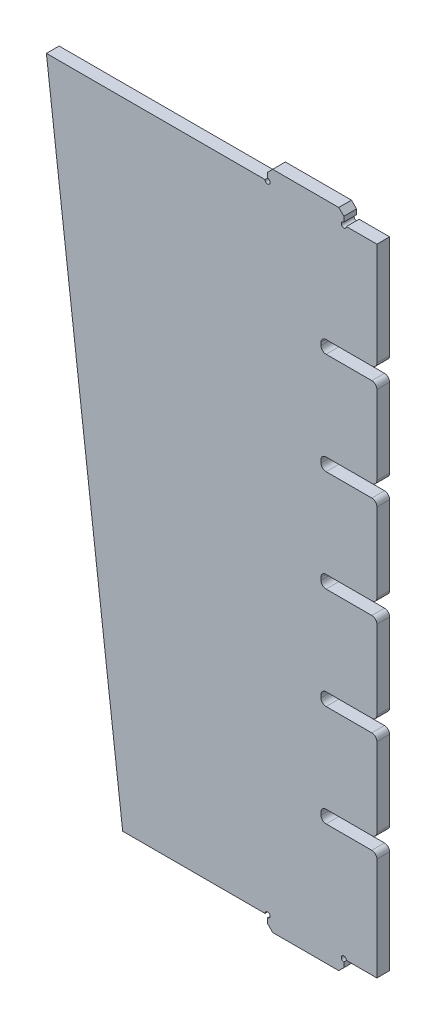
SolidWorks part; units mm, degrees
ref_plane "前基準面" through (0, 0, 0) normal (0, 0, 1) x (1, 0, 0)
ref_plane "上基準面" through (0, 0, 0) normal (0, 1, 0) x (1, 0, 0)
ref_plane "右基準面" through (0, 0, 0) normal (1, 0, 0) x (0, 0, -1)
sketch "草圖1" plane through (0, 0, 0) normal (0, 0, 1) x (1, 0, 0)
  line L0 (-15, 2) -> (-13, 0)
  line L3 (-13, 0) -> (13, 0)
  line L5 (13, 0) -> (15, 2)
  line L6 (-15, 2) -> (-15, 4)
  line L14 (28, 5) -> (28, 47.5)
  line L15 (-16, 5) -> (-72, 5)
  line L16 (15, 2) -> (15, 4)
  line L17 (16, 5) -> (28, 5)
  line L18 (-65, 130) -> (34.3333, 130) construction
  line L19 (16, 255) -> (28, 255)
  line L20 (15, 258) -> (15, 256)
  line L22 (-15, 258) -> (-15, 256)
  line L23 (13, 260) -> (15, 258)
  line L24 (-13, 260) -> (13, 260)
  line L25 (-15, 258) -> (-13, 260)
  line L26 (6, 172.5) -> (28, 172.5)
  line L27 (6, 212.5) -> (28, 212.5)
  line L28 (6, 212.5) -> (6, 207.5)
  line L29 (6, 207.5) -> (28, 207.5)
  line L31 (6, 172.5) -> (6, 167.5)
  line L32 (6, 167.5) -> (28, 167.5)
  line L34 (6, 132.5) -> (28, 132.5)
  line L35 (6, 132.5) -> (6, 127.5)
  line L36 (6, 127.5) -> (28, 127.5)
  line L38 (6, 92.5) -> (28, 92.5)
  line L39 (6, 92.5) -> (6, 87.5)
  line L40 (6, 87.5) -> (28, 87.5)
  line L42 (6, 52.5) -> (28, 52.5)
  line L43 (6, 52.5) -> (6, 47.5)
  line L44 (6, 47.5) -> (28, 47.5)
  line L46 (28, 212.5) -> (28, 255)
  line L47 (28, 172.5) -> (28, 207.5)
  line L48 (28, 132.5) -> (28, 167.5)
  line L49 (28, 92.5) -> (28, 127.5)
  line L50 (28, 52.5) -> (28, 87.5)
  line L51 (-16, 255) -> (-102, 255)
  line L52 (-102, 255) -> (-72, 5)
  arc A0 (-15, 4) -> (-16, 5) centre (-15, 5) ccw
  arc A1 (16, 5) -> (15, 4) centre (15, 5) ccw
  arc A2 (16, 255) -> (15, 256) centre (15, 255) cw
  arc A3 (-15, 256) -> (-16, 255) centre (-15, 255) cw
  point P1 (15, 0)
  point P2 (-15, 0)
  point P8 (0, 0)
  point P30 (-15, 260)
  point P31 (15, 260)
  point P49 (6, 130)
  dimension "D8" = 1
  dimension "D6" = 22
  dimension "D1" = 30
  dimension "D2" = 250
  dimension "D3" = 130
  dimension "D7" = 3
  dimension "D9" = 5
  dimension "D10" = 40
  dimension "D11" = 5
  dimension "D12" = 43
  dimension "D13" = 100
extrude "填料-伸長1" add sketch "草圖1" along normal mid plane 5 contours L52 L15 A0 L6 L0 L3 L5 L16 A1 L17 L14 L44 L43 L42 L50 L40 L39 L38 L49 L36 L35 L34 L48 L32 L31 L26 L47 L29 L28 L27 L46 L19 A2 L20 L23 L24 L25 L22 A3 L51
fillet "圓角1" radius 2 20 edges at (6, 52.5, 0) (6, 47.5, 0) (28, 47.5, 0) (28, 52.5, 0) (6, 92.5, 0) (6, 87.5, 0) (28, 87.5, 0) (28, 92.5, 0) (6, 127.5, 0) (6, 132.5, 0) (28, 127.5, 0) (28, 132.5, 0) (6, 212.5, 0) (6, 207.5, 0) (28, 212.5, 0) (28, 207.5, 0) (28, 167.5, 0) (28, 172.5, 0) (6, 167.5, 0) (6, 172.5, 0)
